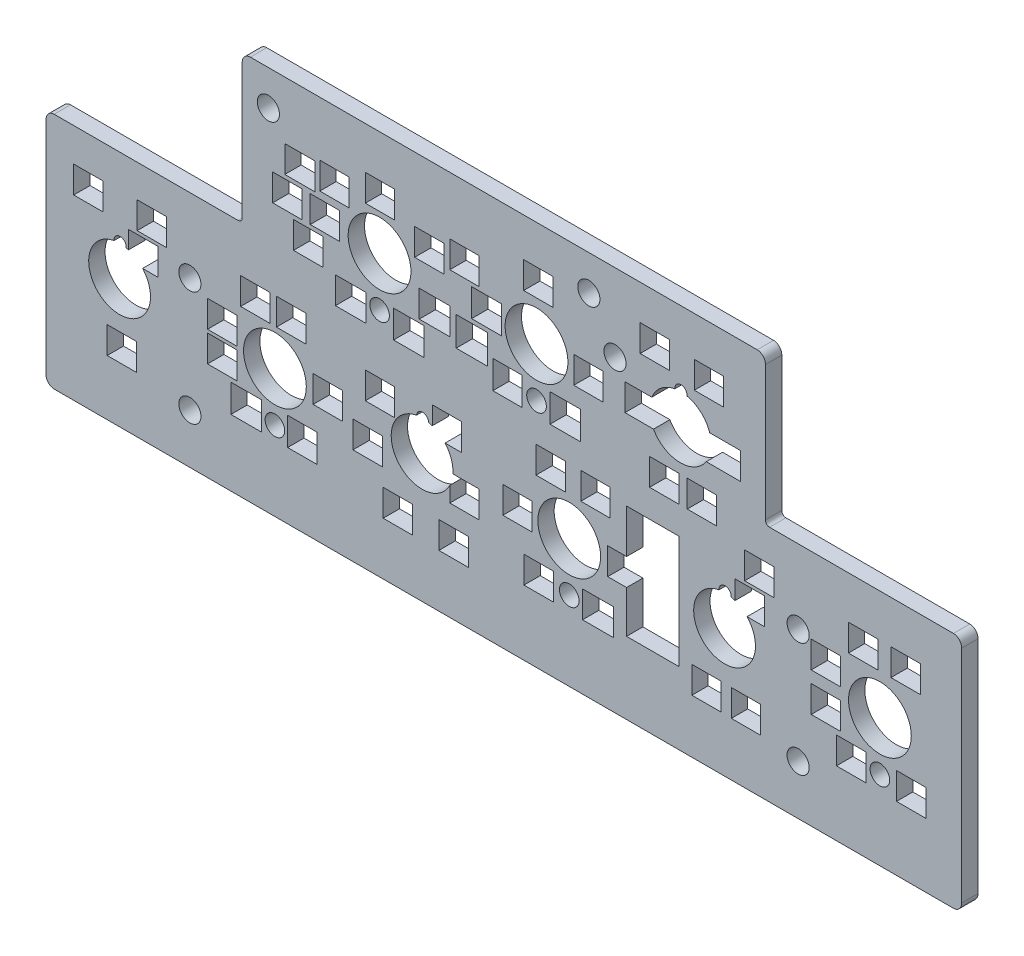
SolidWorks part; units mm, degrees
material "Acrylic (Medium-high impact)"
ref_plane "Front Plane" through (0, 0, 0) normal (0, 0, 1) x (1, 0, 0)
ref_plane "Top Plane" through (0, 0, 0) normal (0, 1, 0) x (1, 0, 0)
ref_plane "Right Plane" through (0, 0, 0) normal (1, 0, 0) x (0, 0, -1)
sketch "Sketch1" plane through (0, 0, 0) normal (0, 0, 1) x (1, 0, 0)
  line L8 (-51.5937, 5.4323) -> (-87.3125, 5.4323)
  line L9 (-88.9, 3.7429) -> (-88.9, -39.0998)
  line L10 (-87.3125, -40.7892) -> (87.3125, -40.7892)
  line L11 (88.9, -39.0998) -> (88.9, 3.7429)
  line L12 (87.3125, 5.4323) -> (51.5938, 5.4323)
  line L13 (50.8, 6.277) -> (50.8, 32.3948)
  line L14 (49.2125, 34.0842) -> (-49.2125, 34.0842)
  line L15 (-50.8, 32.3948) -> (-50.8, 6.277)
  line L16 (-51.5937, 5.4323) -> (-87.3125, 5.4323)
  line L17 (-88.9, 3.7429) -> (-88.9, -39.0998)
  line L18 (-87.3125, -40.7892) -> (87.3125, -40.7892)
  line L19 (88.9, -39.0998) -> (88.9, 3.7429)
  line L20 (87.3125, 5.4323) -> (51.5938, 5.4323)
  line L21 (50.8, 6.277) -> (50.8, 32.3948)
  line L22 (49.2125, 34.0842) -> (-49.2125, 34.0842)
  line L23 (-50.8, 32.3948) -> (-50.8, 6.277)
  ellipse E8 centre (87.3125, 3.7429) end of major axis (87.3125, 2.0535) minor radius 1.5875 (88.9, 3.7429) -> (87.3125, 5.4323) ccw
  ellipse E9 centre (87.3125, 3.7429) end of major axis (87.3125, 2.0535) minor radius 1.5875 (88.9, 3.7429) -> (87.3125, 5.4323) ccw
  ellipse E10 centre (49.2125, 32.3948) end of major axis (49.2125, 34.0842) minor radius 1.5875 (50.8, 32.3948) -> (49.2125, 34.0842) ccw
  ellipse E11 centre (49.2125, 32.3948) end of major axis (49.2125, 34.0842) minor radius 1.5875 (50.8, 32.3948) -> (49.2125, 34.0842) ccw
  ellipse E12 centre (51.5938, 6.277) end of major axis (51.5938, 5.4323) minor radius 0.7938 (50.8, 6.277) -> (51.5938, 5.4323) ccw
  ellipse E13 centre (51.5938, 6.277) end of major axis (51.5938, 5.4323) minor radius 0.7938 (50.8, 6.277) -> (51.5938, 5.4323) ccw
  ellipse E14 centre (-51.5937, 6.277) end of major axis (-51.5937, 5.4323) minor radius 0.7938 (-51.5937, 5.4323) -> (-50.8, 6.277) ccw
  ellipse E15 centre (-51.5937, 6.277) end of major axis (-51.5937, 5.4323) minor radius 0.7938 (-51.5937, 5.4323) -> (-50.8, 6.277) ccw
  ellipse E28 centre (-49.2125, 32.3948) end of major axis (-49.2125, 34.0842) minor radius 1.5875 (-49.2125, 34.0842) -> (-50.8, 32.3948) ccw
  ellipse E29 centre (-49.2125, 32.3948) end of major axis (-49.2125, 34.0842) minor radius 1.5875 (-49.2125, 34.0842) -> (-50.8, 32.3948) ccw
  ellipse E30 centre (-87.3125, 3.7429) end of major axis (-87.3125, 2.0535) minor radius 1.5875 (-87.3125, 5.4323) -> (-88.9, 3.7429) ccw
  ellipse E31 centre (-87.3125, 3.7429) end of major axis (-87.3125, 2.0535) minor radius 1.5875 (-87.3125, 5.4323) -> (-88.9, 3.7429) ccw
  ellipse E32 centre (-87.3125, -39.0998) end of major axis (-87.3125, -37.4104) minor radius 1.5875 (-88.9, -39.0998) -> (-87.3125, -40.7892) ccw
  ellipse E33 centre (-87.3125, -39.0998) end of major axis (-87.3125, -37.4104) minor radius 1.5875 (-88.9, -39.0998) -> (-87.3125, -40.7892) ccw
  ellipse E34 centre (87.3125, -39.0998) end of major axis (87.3125, -37.4104) minor radius 1.5875 (87.3125, -40.7892) -> (88.9, -39.0998) ccw
  ellipse E35 centre (87.3125, -39.0998) end of major axis (87.3125, -37.4104) minor radius 1.5875 (87.3125, -40.7892) -> (88.9, -39.0998) ccw
  dimension "D1" = 0
extrude "Boss-Extrude1" add sketch "Sketch1" along normal blind 3.175
sketch "Sketch2" plane through (0, 0, 3.175) normal (0, 0, 1) x (1, 0, 0)
  arc A4 (-72.0725, -25.0899) -> (-77.1525, -25.0899) centre (-74.6125, -15.9098) ccw construction
  arc A5 (-14.2875, -23.6221) -> (-17.4625, -23.6221) centre (-15.875, -15.9098) ccw construction
  arc A6 (45.4025, -25.0899) -> (40.3225, -25.0899) centre (42.8625, -15.9098) ccw construction
  arc A7 (35.8775, 5.9054) -> (32.7025, 5.9054) centre (34.29, 13.6177) ccw construction
  circle A8 centre (42.8625, -15.9098) radius 3.7703
  circle A9 centre (-15.875, -15.9098) radius 3.7703
  circle A10 centre (-74.6125, -15.9098) radius 3.7703
  circle A11 centre (34.29, 13.6177) radius 3.7703
  dimension "D1" = 7.5406
extrude "Cut-Extrude1" cut sketch "Sketch2" against normal through all
sketch "Sketch4" plane through (0, 0, 3.175) normal (0, 0, 1) x (1, 0, 0)
  circle A0 centre (73.025, -15.9098) radius 6.096
  circle A1 centre (12.7, -15.9098) radius 6.096
  circle A2 centre (-44.45, -15.9098) radius 6.096
  circle A3 centre (-24.13, 13.6177) radius 6.096
  circle A4 centre (6.35, 13.6177) radius 6.096
  circle A5 centre (73.025, -25.4348) radius 1.905
  circle A6 centre (12.7, -25.4348) radius 1.905
  circle A7 centre (-44.45, -25.4348) radius 1.905
  circle A8 centre (6.35, 4.0927) radius 1.905
  circle A9 centre (-24.13, 4.0927) radius 1.905
  dimension "D1" = 12.192
  dimension "D2" = 3.81
  dimension "D3" = 9.525
  dimension "D4" = 9.525
extrude "Cut-Extrude2" cut sketch "Sketch4" against normal through all
hole_wizard "#6 Clearance Hole1" positions "Sketch6" profile "Sketch5" hole size "#6" standard "ANSI Inch" end condition through all
sketch "Sketch6" plane through (0, 0, 3.175) normal (0, 0, 1) x (1, 0, 0)
  point P0 (-45.72, 27.2702)
  point P3 (16.51, 27.2702)
  point P6 (21.59, 19.0152)
  point P9 (57.15, -8.9248)
  point P12 (57.15, -31.1498)
  point P15 (-60.96, -31.1498)
  point P18 (-60.96, -8.9248)
sketch "Sketch5" plane through (-45.72, 27.2702, 3.175) normal (1, 0, 0) x (0, -1, 0)
  line L0 (0, 0) -> (0, 3.175)
  line L1 (0, 3.175) -> (2.1526, 3.175)
  line L2 (2.1526, 3.175) -> (2.1526, 0)
  line L5 (2.1526, 0) -> (0, 0)
  line L11 (0, -6.35) -> (0, 107.95) construction
  dimension "Thru Hole Dia." = 4.3053
  dimension "Thru Hole Depth" = 3.175
fillet "Fillet1" [suppressed] radius 1.5875
sketch "Sketch7" plane through (0, 0, 3.175) normal (0, 0, 1) x (1, 0, 0)
  circle A0 centre (42.967, -9.9107) radius 1.1906
  circle A1 centre (-15.774, -10.1107) radius 1.1906
  circle A2 centre (-74.508, -9.9107) radius 1.1906
  circle A3 centre (34.3945, 19.6168) radius 1.1906
  dimension "D1" = 2.3813
extrude "Cut-Extrude3" cut sketch "Sketch7" against normal through all
sketch "Sketch8" plane through (0, 0, 3.175) normal (0, 0, 1) x (1, 0, 0)
  line L0 (-51.5937, 5.4323) -> (-87.3125, 5.4323)
  line L1 (-50.8, 32.3948) -> (-50.8, 6.277)
  line L2 (49.2125, 34.0842) -> (-49.2125, 34.0842)
  line L3 (50.8, 6.277) -> (50.8, 32.3948)
  line L4 (87.3125, 5.4323) -> (51.5937, 5.4323)
  line L5 (88.9, -39.0998) -> (88.9, 3.7429)
  line L6 (-87.3125, -40.7892) -> (87.3125, -40.7892)
  line L7 (-88.9, 3.7429) -> (-88.9, -39.0998)
  line L8 (-57.5339, -21.6677) -> (-51.8339, -21.6677)
  line L9 (-51.8339, -21.6677) -> (-51.8339, -16.4677)
  line L10 (-51.8339, -16.4677) -> (-57.5339, -16.4677)
  line L11 (-57.5339, -16.4677) -> (-57.5339, -21.6677)
  line L12 (-16.4246, 6.4236) -> (-10.4907, 6.4236)
  line L13 (-10.4907, 6.4236) -> (-10.4907, 11.6236)
  line L14 (-10.4907, 11.6236) -> (-16.4246, 11.6236)
  line L15 (-16.4246, 11.6236) -> (-16.4246, 6.4236)
  line L16 (3.8516, 21.3751) -> (9.5516, 21.3751)
  line L17 (9.5516, 21.3751) -> (9.5516, 26.5751)
  line L18 (9.5516, 26.5751) -> (3.8516, 26.5751)
  line L19 (3.8516, 26.5751) -> (3.8516, 21.3751)
  line L20 (-2.1329, 1.5322) -> (3.5671, 1.5322)
  line L21 (3.5671, 1.5322) -> (3.5671, 6.9801)
  line L22 (3.5671, 6.9801) -> (-2.1329, 6.9801)
  line L23 (-2.1329, 6.9801) -> (-2.1329, 1.5322)
  line L24 (13.5869, 10.3093) -> (19.2869, 10.3093)
  line L25 (19.2869, 10.3093) -> (19.2869, 15.5093)
  line L26 (19.2869, 15.5093) -> (13.5869, 15.5093)
  line L27 (13.5869, 15.5093) -> (13.5869, 10.3093)
  line L28 (-23.4257, -30.562) -> (-17.7257, -30.562)
  line L29 (-17.7257, -30.562) -> (-17.7257, -25.362)
  line L30 (-17.7257, -25.362) -> (-23.4257, -25.362)
  line L31 (-23.4257, -25.362) -> (-23.4257, -30.562)
  line L32 (-17.3237, 16.3707) -> (-11.6237, 16.3707)
  line L33 (-11.6237, 16.3707) -> (-11.6237, 21.5707)
  line L34 (-11.6237, 21.5707) -> (-17.3237, 21.5707)
  line L35 (-17.3237, 21.5707) -> (-17.3237, 16.3707)
  line L36 (-26.8936, 20.6839) -> (-21.1936, 20.6839)
  line L37 (-21.1936, 20.6839) -> (-21.1936, 25.8839)
  line L38 (-21.1936, 25.8839) -> (-26.8936, 25.8839)
  line L39 (-26.8936, 25.8839) -> (-26.8936, 20.6839)
  line L40 (-6.2605, 11.5858) -> (-0.4348, 11.5858)
  line L41 (-0.4348, 11.5858) -> (-0.4348, 16.9765)
  line L42 (-0.4348, 16.9765) -> (-6.2605, 16.9765)
  line L43 (-6.2605, 16.9765) -> (-6.2605, 11.5858)
  line L44 (3.902, -28.1405) -> (9.602, -28.1405)
  line L45 (9.602, -28.1405) -> (9.602, -22.9405)
  line L46 (9.602, -22.9405) -> (3.902, -22.9405)
  line L47 (3.902, -22.9405) -> (3.902, -28.1405)
  line L48 (20.173, -18.5822) -> (23.8341, -18.5822)
  line L50 (23.8341, -13.3822) -> (20.173, -13.3822)
  line L51 (20.173, -13.3822) -> (20.173, -18.5822)
  line L52 (-0.184, -18.4363) -> (5.516, -18.4363)
  line L53 (5.516, -18.4363) -> (5.516, -13.2363)
  line L54 (5.516, -13.2363) -> (-0.184, -13.2363)
  line L55 (-0.184, -13.2363) -> (-0.184, -18.4363)
  line L56 (6.2437, -8.4752) -> (11.9437, -8.4752)
  line L57 (11.9437, -8.4752) -> (11.9437, -3.2752)
  line L58 (11.9437, -3.2752) -> (6.2437, -3.2752)
  line L59 (6.2437, -3.2752) -> (6.2437, -8.4752)
  line L60 (23.5207, 10.6712) -> (29.0633, 10.6712)
  line L62 (28.7293, 15.8712) -> (23.5207, 15.8712)
  line L63 (23.5207, 15.8712) -> (23.5207, 10.6712)
  line L64 (40.2759, 10.3093) -> (45.9759, 10.3093)
  line L65 (45.9759, 10.3093) -> (45.9759, 15.5093)
  line L66 (45.9759, 15.5093) -> (40.2759, 15.5093)
  line L68 (36.9852, 21.1664) -> (42.6852, 21.1664)
  line L69 (42.6852, 21.1664) -> (42.6852, 26.3664)
  line L70 (42.6852, 26.3664) -> (36.9852, 26.3664)
  line L71 (36.9852, 26.3664) -> (36.9852, 21.1664)
  line L72 (26.4638, 22.0824) -> (32.1638, 22.0824)
  line L73 (32.1638, 22.0824) -> (32.1638, 27.2824)
  line L74 (32.1638, 27.2824) -> (26.4638, 27.2824)
  line L75 (26.4638, 27.2824) -> (26.4638, 22.0824)
  line L76 (-29.302, -22.0056) -> (-23.602, -22.0056)
  line L77 (-23.602, -22.0056) -> (-23.602, -16.8056)
  line L78 (-23.602, -16.8056) -> (-29.302, -16.8056)
  line L79 (-29.302, -16.8056) -> (-29.302, -22.0056)
  line L80 (-26.8936, -12.5459) -> (-21.1936, -12.5459)
  line L81 (-21.1936, -12.5459) -> (-21.1936, -7.3459)
  line L82 (-21.1936, -7.3459) -> (-26.8936, -7.3459)
  line L83 (-26.8936, -7.3459) -> (-26.8936, -12.5459)
  line L84 (-10.4862, -21.537) -> (-4.7862, -21.537)
  line L85 (-4.7862, -21.537) -> (-4.7862, -16.337)
  line L86 (-4.7862, -16.337) -> (-9.8902, -16.337)
  line L87 (-10.4862, -18.5481) -> (-10.4862, -21.537)
  line L88 (-11.4038, -11.9088) -> (-8.1877, -11.9088)
  line L89 (-8.1877, -11.9088) -> (-8.1877, -6.7088)
  line L90 (-8.1877, -6.7088) -> (-13.8877, -6.7088)
  line L91 (-13.8877, -6.7088) -> (-13.8877, -10.2485)
  line L92 (-51.1023, -8.787) -> (-45.4023, -8.787)
  line L93 (-45.4023, -8.787) -> (-45.4023, -3.587)
  line L94 (-45.4023, -3.587) -> (-51.1023, -3.587)
  line L95 (-51.1023, -3.587) -> (-51.1023, -8.787)
  line L96 (-37.0315, -18.226) -> (-31.3315, -18.226)
  line L97 (-31.3315, -18.226) -> (-31.3315, -13.026)
  line L98 (-31.3315, -13.026) -> (-37.0315, -13.026)
  line L99 (-37.0315, -13.026) -> (-37.0315, -18.226)
  line L100 (-70.1435, -11.9063) -> (-67.1781, -11.9063)
  line L101 (-67.1781, -11.9063) -> (-67.1781, -6.7063)
  line L102 (-67.1781, -6.7063) -> (-72.8781, -6.7063)
  line L103 (-72.8781, -6.7063) -> (-72.8781, -10.1659)
  line L104 (-71.2049, -6.0898) -> (-65.5049, -6.0898)
  line L105 (-65.5049, -6.0898) -> (-65.5049, -0.8898)
  line L106 (-65.5049, -0.8898) -> (-71.2049, -0.8898)
  line L107 (-71.2049, -0.8898) -> (-71.2049, -6.0898)
  line L108 (64.5921, -28.1957) -> (70.2921, -28.1957)
  line L109 (70.2921, -28.1957) -> (70.2921, -22.9957)
  line L110 (70.2921, -22.9957) -> (64.5921, -22.9957)
  line L111 (64.5921, -22.9957) -> (64.5921, -28.1957)
  line L112 (-37.5953, 11.7476) -> (-31.8953, 11.7476)
  line L113 (-31.8953, 11.7476) -> (-31.8953, 16.9476)
  line L114 (-31.8953, 16.9476) -> (-37.5953, 16.9476)
  line L115 (-37.5953, 16.9476) -> (-37.5953, 11.7476)
  line L116 (-9.2553, 5.1211) -> (-3.1441, 5.1211)
  line L117 (-3.1441, 5.1211) -> (-3.1441, 10.7909)
  line L118 (-3.1441, 10.7909) -> (-9.2553, 10.7909)
  line L119 (-9.2553, 10.7909) -> (-9.2553, 5.1211)
  line L120 (-21.4064, 0.4179) -> (-15.468, 0.4179)
  line L121 (-15.468, 0.4179) -> (-15.468, 5.7877)
  line L122 (-15.468, 5.7877) -> (-21.4064, 5.7877)
  line L123 (-21.4064, 5.7877) -> (-21.4064, 0.4179)
  line L124 (59.6809, -22.0056) -> (65.3809, -22.0056)
  line L125 (65.3809, -22.0056) -> (65.3809, -16.8056)
  line L126 (65.3809, -16.8056) -> (59.6809, -16.8056)
  line L127 (59.6809, -16.8056) -> (59.6809, -22.0056)
  line L128 (-35.7321, 18.305) -> (-30.0321, 18.305)
  line L129 (-30.0321, 18.305) -> (-30.0321, 23.505)
  line L130 (-30.0321, 23.505) -> (-35.7321, 23.505)
  line L131 (-35.7321, 23.505) -> (-35.7321, 18.305)
  line L132 (-32.7001, 0.5426) -> (-26.7664, 0.5426)
  line L133 (-26.7664, 0.5426) -> (-26.7664, 5.7426)
  line L134 (-26.7664, 5.7426) -> (-32.7001, 5.7426)
  line L135 (-32.7001, 5.7426) -> (-32.7001, 0.5426)
  line L136 (-57.5339, -15.8363) -> (-51.8339, -15.8363)
  line L137 (-51.8339, -15.8363) -> (-51.8339, -10.6363)
  line L138 (-51.8339, -10.6363) -> (-57.5339, -10.6363)
  line L139 (-57.5339, -10.6363) -> (-57.5339, -15.8363)
  line L140 (-77.0213, -29.9931) -> (-71.3213, -29.9931)
  line L141 (-71.3213, -29.9931) -> (-71.3213, -24.7931)
  line L142 (-71.3213, -24.7931) -> (-77.0213, -24.7931)
  line L143 (-77.0213, -24.7931) -> (-77.0213, -29.9931)
  line L144 (-41.9767, -27.9461) -> (-36.2767, -27.9461)
  line L145 (-36.2767, -27.9461) -> (-36.2767, -22.5204)
  line L146 (-36.2767, -22.5204) -> (-41.9767, -22.5204)
  line L147 (-41.9767, -22.5204) -> (-41.9767, -27.9461)
  line L148 (76.2478, -28.3416) -> (81.9478, -28.3416)
  line L149 (81.9478, -28.3416) -> (81.9478, -23.1416)
  line L150 (81.9478, -23.1416) -> (76.2478, -23.1416)
  line L151 (76.2478, -23.1416) -> (76.2478, -28.3416)
  line L152 (-40.8349, 5.7772) -> (-35.1349, 5.7772)
  line L153 (-35.1349, 5.7772) -> (-35.1349, 10.9772)
  line L154 (-35.1349, 10.9772) -> (-40.8349, 10.9772)
  line L155 (-40.8349, 10.9772) -> (-40.8349, 5.7772)
  line L156 (-83.5151, -6.2491) -> (-77.8151, -6.2491)
  line L157 (-77.8151, -6.2491) -> (-77.8151, -1.0491)
  line L158 (-77.8151, -1.0491) -> (-83.5151, -1.0491)
  line L159 (-83.5151, -1.0491) -> (-83.5151, -6.2491)
  line L160 (-44.1583, -8.787) -> (-38.4583, -8.787)
  line L161 (-38.4583, -8.787) -> (-38.4583, -3.587)
  line L162 (-38.4583, -3.587) -> (-44.1583, -3.587)
  line L163 (-44.1583, -3.587) -> (-44.1583, -8.787)
  line L164 (-52.9981, -27.8943) -> (-47.0898, -27.8943)
  line L165 (-47.0898, -27.8943) -> (-47.0898, -22.463)
  line L166 (-47.0898, -22.463) -> (-52.9981, -22.463)
  line L167 (-52.9981, -22.463) -> (-52.9981, -27.8943)
  line L168 (15.2844, -28.2864) -> (21.2964, -28.2864)
  line L169 (21.2964, -28.2864) -> (21.2964, -23.0864)
  line L170 (21.2964, -23.0864) -> (15.2844, -23.0864)
  line L171 (15.2844, -23.0864) -> (15.2844, -28.2864)
  line L172 (-44.8849, 11.7476) -> (-39.1849, 11.7476)
  line L173 (-39.1849, 11.7476) -> (-39.1849, 16.9476)
  line L174 (-39.1849, 16.9476) -> (-44.8849, 16.9476)
  line L175 (-44.8849, 16.9476) -> (-44.8849, 11.7476)
  line L176 (75.1693, -8.0633) -> (80.8693, -8.0633)
  line L177 (80.8693, -8.0633) -> (80.8693, -2.8633)
  line L178 (80.8693, -2.8633) -> (75.1693, -2.8633)
  line L179 (75.1693, -2.8633) -> (75.1693, -8.0633)
  line L180 (44.1756, -30.4188) -> (49.8756, -30.4188)
  line L181 (49.8756, -30.4188) -> (49.8756, -25.2188)
  line L182 (49.8756, -25.2188) -> (44.1756, -25.2188)
  line L183 (44.1756, -25.2188) -> (44.1756, -30.4188)
  line L184 (47.2241, -11.7896) -> (50.5854, -11.7896)
  line L185 (50.5854, -11.7896) -> (50.5854, -6.5896)
  line L186 (50.5854, -6.5896) -> (44.8854, -6.5896)
  line L187 (44.8854, -6.5896) -> (44.8854, -10.2611)
  line L188 (28.302, 0.5017) -> (34.002, 0.5017)
  line L189 (34.002, 0.5017) -> (34.002, 5.7017)
  line L190 (34.002, 5.7017) -> (28.302, 5.7017)
  line L191 (28.302, 5.7017) -> (28.302, 0.5017)
  line L192 (46.7612, -5.9836) -> (52.4612, -5.9836)
  line L193 (52.4612, -5.9836) -> (52.4612, -0.7836)
  line L194 (52.4612, -0.7836) -> (46.7612, -0.7836)
  line L195 (46.7612, -0.7836) -> (46.7612, -5.9836)
  line L196 (36.5158, -30.3563) -> (42.2158, -30.3563)
  line L197 (42.2158, -30.3563) -> (42.2158, -25.1563)
  line L198 (42.2158, -25.1563) -> (36.5158, -25.1563)
  line L199 (36.5158, -25.1563) -> (36.5158, -30.3563)
  line L200 (8.9659, 1.4426) -> (14.8998, 1.4426)
  line L201 (14.8998, 1.4426) -> (14.8998, 6.9217)
  line L202 (14.8998, 6.9217) -> (8.9659, 6.9217)
  line L203 (8.9659, 6.9217) -> (8.9659, 1.4426)
  line L204 (59.6809, -14.5136) -> (65.3809, -14.5136)
  line L205 (65.3809, -14.5136) -> (65.3809, -9.3136)
  line L206 (65.3809, -9.3136) -> (59.6809, -9.3136)
  line L207 (59.6809, -9.3136) -> (59.6809, -14.5136)
  line L208 (-10.4862, 17.696) -> (-4.7862, 17.696)
  line L209 (-4.7862, 17.696) -> (-4.7862, 22.896)
  line L210 (-4.7862, 22.896) -> (-10.4862, 22.896)
  line L211 (-10.4862, 22.896) -> (-10.4862, 17.696)
  line L212 (35.615, 0.5017) -> (41.315, 0.5017)
  line L213 (41.315, 0.5017) -> (41.315, 5.7017)
  line L214 (41.315, 5.7017) -> (35.615, 5.7017)
  line L215 (35.615, 5.7017) -> (35.615, 0.5017)
  line L216 (-12.6071, -30.562) -> (-6.9071, -30.562)
  line L217 (-6.9071, -30.562) -> (-6.9071, -25.362)
  line L218 (-6.9071, -25.362) -> (-12.6071, -25.362)
  line L219 (-12.6071, -25.362) -> (-12.6071, -30.562)
  line L220 (-42.534, 17.696) -> (-36.6383, 17.696)
  line L221 (-36.6383, 17.696) -> (-36.6383, 22.896)
  line L222 (-36.6383, 22.896) -> (-42.534, 22.896)
  line L223 (-42.534, 22.896) -> (-42.534, 17.696)
  line L224 (66.9091, -8.0633) -> (72.6091, -8.0633)
  line L225 (72.6091, -8.0633) -> (72.6091, -2.8633)
  line L226 (72.6091, -2.8633) -> (66.9091, -2.8633)
  line L227 (66.9091, -2.8633) -> (66.9091, -8.0633)
  line L228 (14.9533, -8.5151) -> (20.6533, -8.5151)
  line L229 (20.6533, -8.5151) -> (20.6533, -3.3151)
  line L230 (20.6533, -3.3151) -> (14.9533, -3.3151)
  line L231 (14.9533, -3.3151) -> (14.9533, -8.5151)
  line L233 (40.2759, 15.5093) -> (39.984, 15.5093)
  line L234 (40.2759, 10.3093) -> (39.2955, 10.3093)
  line L235 (23.8341, -18.5822) -> (23.8341, -26.7937)
  line L236 (23.8341, -4.8729) -> (34.002, -4.8729)
  line L237 (23.8341, -4.8729) -> (23.8341, -13.3822)
  line L238 (23.8341, -26.7937) -> (34.002, -26.7937)
  line L239 (34.002, -4.8729) -> (34.002, -26.7937)
  circle A0 centre (42.8625, -15.9098) radius 3.7703
  circle A1 centre (-15.875, -15.9098) radius 3.7703
  circle A2 centre (-74.6125, -15.9098) radius 3.7703
  circle A3 centre (34.29, 13.6177) radius 3.7703
  circle A4 centre (73.025, -15.9098) radius 6.096
  circle A5 centre (12.7, -15.9098) radius 6.096
  circle A6 centre (-44.45, -15.9098) radius 6.096
  circle A7 centre (-24.13, 13.6177) radius 6.096
  circle A8 centre (6.35, 13.6177) radius 6.096
  circle A9 centre (73.025, -25.4348) radius 1.905
  circle A10 centre (12.7, -25.4348) radius 1.905
  circle A11 centre (-44.45, -25.4348) radius 1.905
  circle A12 centre (6.35, 4.0927) radius 1.905
  circle A13 centre (-24.13, 4.0927) radius 1.905
  circle A14 centre (-60.96, -8.9248) radius 2.1527
  circle A15 centre (-60.96, -31.1498) radius 2.1527
  circle A16 centre (57.15, -31.1498) radius 2.1526
  circle A17 centre (57.15, -8.9248) radius 2.1526
  circle A18 centre (21.59, 19.0152) radius 2.1527
  circle A19 centre (16.51, 27.2702) radius 2.1526
  circle A20 centre (-45.72, 27.2702) radius 2.1527
  circle A21 centre (34.3945, 19.6168) radius 1.1906
  circle A22 centre (-74.508, -9.9107) radius 1.1906
  circle A23 centre (-15.774, -10.1107) radius 1.1906
  circle A24 centre (42.967, -9.9107) radius 1.1906
  arc A25 (-51.5937, 5.4323) -> (-50.8, 6.277) centre (-51.619, 6.2513) ccw
  arc A26 (-49.2125, 34.0842) -> (-50.8, 32.3948) centre (-49.1599, 32.4443) ccw
  arc A27 (50.8, 32.3948) -> (49.2125, 34.0842) centre (49.1599, 32.4443) ccw
  arc A28 (50.8, 6.277) -> (51.5937, 5.4323) centre (51.6211, 6.2533) ccw
  arc A29 (88.9, 3.7429) -> (87.3125, 5.4323) centre (87.2599, 3.7923) ccw
  arc A30 (87.3125, -40.7892) -> (88.9, -39.0998) centre (87.2599, -39.1492) ccw
  arc A31 (-88.9, -39.0998) -> (-87.3125, -40.7892) centre (-87.2621, -39.1512) ccw
  arc A32 (-87.3125, 5.4323) -> (-88.9, 3.7429) centre (-87.2599, 3.7923) ccw
  arc A33 (44.8854, -10.2611) -> (47.2241, -11.7896) centre (42.8625, -15.9098) ccw
  arc A34 (-9.8902, -16.337) -> (-11.4038, -11.9088) centre (-15.875, -15.9098) ccw
  arc A35 (-72.8781, -10.1659) -> (-70.1435, -11.9063) centre (-74.6125, -15.9098) ccw
  arc A36 (29.0633, 10.6712) -> (39.2955, 10.3093) centre (34.29, 13.6177) ccw
  arc A37 (-13.8877, -10.2485) -> (-10.4862, -18.5481) centre (-15.875, -15.9098) ccw
  arc A38 (39.984, 15.5093) -> (28.7293, 15.8712) centre (34.29, 13.6177) ccw
  point P308 (25.3448, -4.905)
  point P309 (24.6698, -5.9014)
  point P310 (24.0913, -4.8729)
  point P311 (23.8341, -26.7937)
  dimension "D1" = 12
  dimension "D2" = 12
  dimension "D3" = 12
  dimension "D4" = 12
extrude "Backlighting LED holes" cut sketch "Sketch8" against normal up to next (3.175 mm away) contours L150 L151 L148 L149 | L110 L111 L108 L109 | L126 L127 L124 L125 | L206 L207 L204 L205 | L226 L227 L224 L225 | L178 L179 L176 L177 | L182 L183 L180 L181 | L198 L199 L196 L197 | L186 L187 L184 L185 | L194 L195 L192 L193 | L170 L171 L168 L169 | L50 L51 L48 | L230 L231 L228 L229 | L58 L59 L56 L57 | L54 L55 L52 L53 | L46 L47 L44 L45 | L86 L87 L84 L85 | L218 L219 L216 L217 | L30 L31 L28 L29 | L78 L79 L76 L77 | L82 L83 L80 L81 | L90 L91 L88 L89 | L98 L99 L96 L97 | L146 L147 L144 L145 | L162 L163 L160 L161 | L94 L95 L92 L93 | L166 L167 L164 L165 | L10 L11 L8 L9 | L138 L139 L136 L137 | L102 L103 L100 L101 | L106 L107 L104 L105 | L158 L159 L156 L157 | L142 L143 L140 L141 | L154 L155 L152 L153 | L114 L115 L112 L113 | L130 L131 L128 L129 | L222 L223 L220 L221 | L174 L175 L172 L173 | L134 L135 L132 L133 | L122 L123 L120 L121 | L14 L15 L12 L13 | L34 L35 L32 L33 | L38 L39 L36 L37 | L210 L211 L208 L209 | L42 L43 L40 L41 | L118 L119 L116 L117 | L22 L23 L20 L21 | L202 L203 L200 L201 | L26 L27 L24 L25 | L18 L19 L16 L17 | L62 L63 L60 | L190 L191 L188 L189 | L214 L215 L212 L213 | L66 L64 L65 | L70 L71 L68 L69 | L74 L75 L72 L73 region at (-54.6839, -19.0677, 3.175) region at (-13.4576, 9.0236, 3.175) region at (6.7016, 23.9751, 3.175) region at (0.7171, 4.2562, 3.175) region at (16.4369, 12.9093, 3.175) region at (-20.5757, -27.962, 3.175) region at (-14.4737, 18.9707, 3.175) region at (-24.0436, 23.2839, 3.175) region at (-3.3476, 14.2812, 3.175) region at (6.752, -25.5405, 3.175) region at (28.374, -15.845, 3.175) region at (2.666, -15.8363, 3.175) region at (9.0937, -5.8752, 3.175) region at (23.7748, 13.2712, 3.175) region at (39.8352, 23.7664, 3.175) region at (29.3138, 24.6824, 3.175) region at (-26.452, -19.4056, 3.175) region at (-24.0436, -9.9459, 3.175) region at (-10.2575, -20.0425, 3.175) region at (-48.2523, -6.187, 3.175) region at (-34.1815, -15.626, 3.175) region at (-76.4881, -21.3951, 3.175) region at (-68.3549, -3.4898, 3.175) region at (67.4421, -25.5957, 3.175) region at (-34.7453, 14.3476, 3.175) region at (-6.1997, 7.956, 3.175) region at (-18.4372, 3.1028, 3.175) region at (62.5309, -19.4056, 3.175) region at (-32.8821, 20.905, 3.175) region at (-29.7333, 3.1426, 3.175) region at (-54.6839, -13.2363, 3.175) region at (-74.1713, -27.3931, 3.175) region at (-39.1267, -25.2332, 3.175) region at (79.0978, -25.7416, 3.175) region at (-37.9849, 8.3772, 3.175) region at (-80.6651, -3.6491, 3.175) region at (-41.3083, -6.187, 3.175) region at (-50.044, -25.1787, 3.175) region at (18.2904, -25.6864, 3.175) region at (-42.0349, 14.3476, 3.175) region at (78.0193, -5.4633, 3.175) region at (47.0256, -27.8188, 3.175) region at (41.0604, -21.4168, 3.175) region at (31.152, 3.1017, 3.175) region at (49.6112, -3.3836, 3.175) region at (39.3658, -27.7563, 3.175) region at (11.9329, 4.1822, 3.175) region at (62.5309, -11.9136, 3.175) region at (-7.6362, 20.296, 3.175) region at (38.465, 3.1017, 3.175) region at (-9.7571, -27.962, 3.175) region at (-39.5862, 20.296, 3.175) region at (69.7591, -5.4633, 3.175) region at (17.8033, -5.9151, 3.175)
equation "\"D4@Sketch4\"=\"D3@Sketch4\""
